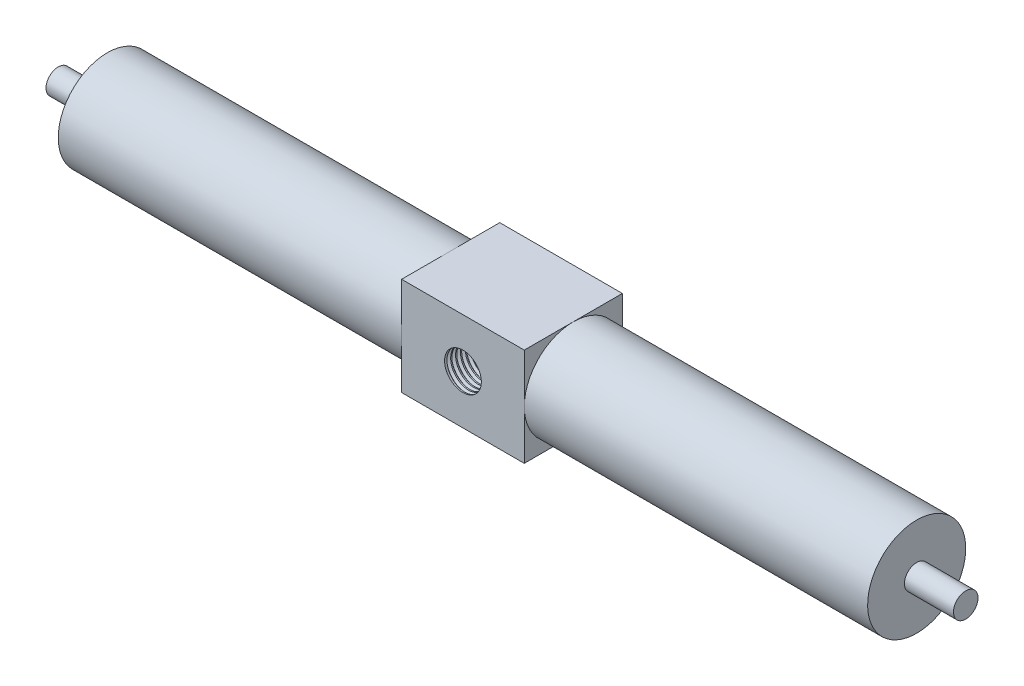
SolidWorks part; units mm, degrees
ref_plane "Front Plane" through (0, 0, 0) normal (0, 0, 1) x (1, 0, 0)
ref_plane "Top Plane" through (0, 0, 0) normal (0, 1, 0) x (1, 0, 0)
ref_plane "Right Plane" through (0, 0, 0) normal (1, 0, 0) x (0, 0, -1)
sketch "Sketch1" plane through (0, 0, 0) normal (0, 0, 1) x (1, 0, 0)
  line L0 (203.6676, 133.4309) -> (-166.3324, 133.4309)
  line L10 (203.6676, 133.4309) -> (203.6676, 138.4309)
  line L13 (-166.3324, 133.4309) -> (157.6676, 133.4309) construction
  line L14 (203.6676, 138.4309) -> (183.6676, 138.4309)
  line L15 (183.6676, 138.4309) -> (183.6676, 153.4309)
  line L21 (-166.3324, 133.4309) -> (-166.3324, 138.4309)
  line L22 (-166.3324, 138.4309) -> (-146.3324, 138.4309)
  line L23 (-146.3324, 138.4309) -> (-146.3324, 153.4309)
  line L24 (183.6676, 153.4309) -> (-146.3324, 153.4309)
  point P17 (18.6676, 133.4309)
  point P20 (-34.5089, 153.4309)
  dimension "D1" = 20
  dimension "D3" = 20
  dimension "D5" = 330
revolve "Revolve2" add sketch "Sketch1" angle 360 about L0
sketch "Sketch4" plane through (0, 0, 0) normal (0, 0, 1) x (1, 0, 0)
  line L1 (-6.3324, 153.4309) -> (43.6676, 153.4309)
  line L2 (-6.3324, 153.4309) -> (-6.3324, 113.4309)
  line L3 (-6.3324, 113.4309) -> (43.6676, 113.4309)
  line L4 (43.6676, 153.4309) -> (43.6676, 113.4309)
  line L5 (-6.3324, 153.4309) -> (43.6676, 113.4309) construction
  line L6 (-6.3324, 113.4309) -> (43.6676, 153.4309) construction
  point P0 (18.6676, 133.4309)
  dimension "D2" = 50
extrude "Boss-Extrude2" add sketch "Sketch4" along normal mid plane 40
sketch "Sketch5" plane through (0, 0, 20) normal (0, 0, 1) x (1, 0, 0)
  circle A0 centre (18.6676, 133.4309) radius 7.5
  dimension "D1" = 15
extrude "Cut-Extrude2" cut sketch "Sketch5" against normal blind 58
thread "Thread2" pitch 2 method cut profile "Thread Profile2" start angle 180, offset 0, length 40, pitch 2, diameter 15
ref_plane "Plane2" through (26.1676, 133.4309, 20) normal (0, 1, 0) x (1, 0, 0)
sketch "Thread Profile2" plane through (26.1676, 133.4309, 20) normal (0, 1, 0) x (1, 0, 0)
  line L0 (0, 0) -> (0, 2) construction
  line L1 (0, 0) -> (1.0825, 0.625)
  line L2 (1.0825, 0.625) -> (1.0825, 0.875)
  line L3 (1.0825, 0.875) -> (0, 1.5)
  line L4 (1.0825, 0.75) -> (0, 0.75) construction
  line L11 (0, 0) -> (0, 1.5)
  point P2 (0, 0)
  dimension "Pitch" = 2
  dimension "Profile_Angle" = 60
  dimension "Profile_Land" = 0.25
  dimension "Profile_Height" = 1.0825
